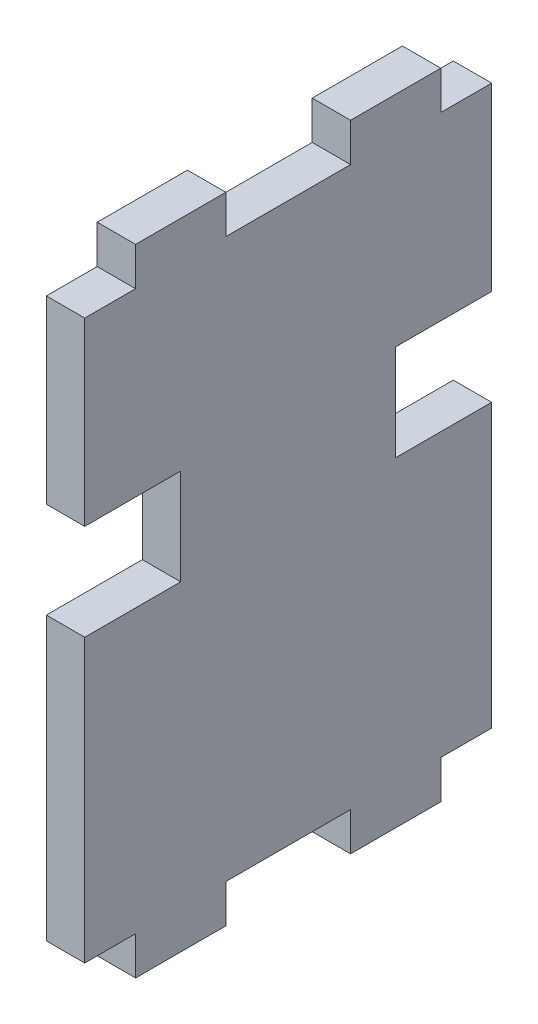
SolidWorks part; units mm, degrees
ref_plane "Front Plane" through (0, 0, 0) normal (0, 0, 1) x (1, 0, 0)
ref_plane "Top Plane" through (0, 0, 0) normal (0, 1, 0) x (1, 0, 0)
ref_plane "Right Plane" through (0, 0, 0) normal (1, 0, 0) x (0, 0, -1)
sketch "Sketch1" plane through (0, 0, 0) normal (0, 1, 0) x (1, 0, 0)
  line L1 (0, 0) -> (20, 0)
  line L2 (0, 0) -> (0, 50)
  line L3 (0, 50) -> (20, 50)
  line L4 (20, 0) -> (20, 50)
  dimension "D1" = 50
  dimension "D2" = 20
extrude "Boss-Extrude2" add sketch "Sketch1" along normal blind 4
sketch "Sketch3" plane through (0, 4, 0) normal (0, 1, 0) x (1, 0, 0)
  line L0 (7.85, 10.95) -> (6.4, 25)
  line L1 (6.4, 25) -> (7.85, 39.05)
  line L2 (12.15, 39.05) -> (13.6, 25)
  line L3 (13.6, 25) -> (12.15, 10.95)
  line L4 (6.4, 25) -> (13.6, 25) construction
  line L5 (20, 50) -> (0, 50) construction
  line L6 (0, 50) -> (0, 0) construction
  arc A0 (12.15, 39.05) -> (7.85, 39.05) centre (10, 39.05) ccw
  arc A1 (7.85, 10.95) -> (12.15, 10.95) centre (10, 10.95) ccw
  point P12 (10, 50)
  point P15 (0, 25)
  dimension "D1" = 4.3
  dimension "D2" = 4.3
  dimension "D3" = 28.1
  dimension "D4" = 14.05
  dimension "D5" = 7.2
  dimension "D6" = 3.6
  dimension "D7" = 3.6
extrude "Cut-Extrude1" cut sketch "Sketch3" against normal blind 2
sketch "Sketch7" plane through (0, 4, 0) normal (0, 1, 0) x (1, 0, 0)
  line L0 (17.1141, 39.7659) -> (18.6, 25)
  line L1 (18.6, 25) -> (17.1141, 10.2341)
  line L4 (10, 46.2) -> (0, 46.2)
  line L5 (0, 50) -> (0, 0) construction
  line L6 (10, 3.8) -> (0, 3.8)
  line L7 (0, 3.8) -> (0, 0)
  line L8 (20, 50) -> (0, 50)
  line L9 (20, 50) -> (20, 0)
  line L10 (20, 0) -> (0, 0)
  line L11 (0, 50) -> (0, 46.2)
  arc A0 (17.1141, 39.7659) -> (10, 46.2) centre (10, 39.05) ccw
  arc A1 (10, 3.8) -> (17.1141, 10.2341) centre (10, 10.95) ccw
  arc A3 (12.15, 39.05) -> (7.85, 39.05) centre (10, 39.05) ccw construction
  arc A4 (7.85, 10.95) -> (12.15, 10.95) centre (10, 10.95) ccw construction
  dimension "D1" = 5
  dimension "D2" = 5
  dimension "D3" = 5
extrude "Cut-Extrude2" cut sketch "Sketch7" against normal through all both and the other way through all
sketch "Sketch8" plane through (0, 0, 0) normal (0, -1, 0) x (1, 0, 0)
  line L1 (0, -46.2) -> (-64.2367, -46.2)
  line L2 (0, -46.2) -> (0, -3.8)
  line L3 (0, -3.8) -> (-64.2367, -3.8)
  line L4 (-64.2367, -46.2) -> (-64.2367, -3.8)
extrude "Boss-Extrude4" add sketch "Sketch8" against normal blind 4
sketch "Sketch9" plane through (0, 2, 0) normal (0, 1, 0) x (1, 0, 0)
  circle A0 centre (10, 25) radius 1.7
  dimension "D1" = 3.4
  dimension "D2" = 3.6
extrude "Cut-Extrude4" cut sketch "Sketch9" against normal blind 4
sketch "Sketch10" plane through (0, 0, 0) normal (0, -1, 0) x (1, 0, 0)
  line L0 (-64.2367, -46.2) -> (10, -46.2) construction
  line L1 (-64.2367, -3.8) -> (-11, -3.8)
  line L2 (-64.2367, -3.8) -> (-64.2367, -46.2)
  line L3 (-64.2367, -46.2) -> (-11, -46.2)
  line L4 (-11, -3.8) -> (-11, -46.2)
  circle A0 centre (10, -25) radius 1.7
  dimension "D1" = 21
extrude "Cut-Extrude5" cut sketch "Sketch10" against normal blind 4
sketch "Sketch11" plane through (0, 0, 0) normal (0, -1, 0) x (1, 0, 0)
  line L0 (-11, -46.2) -> (10, -46.2) construction
  line L1 (-11, -3.8) -> (-5, -3.8)
  line L2 (-11, -3.8) -> (-11, -46.2)
  line L3 (-11, -46.2) -> (-5, -46.2)
  line L4 (-5, -3.8) -> (-5, -46.2)
  dimension "D1" = 6
extrude "Boss-Extrude5" add sketch "Sketch11" along normal blind 62.2
sketch "Sketch13" plane through (-5, 0, 0) normal (1, 0, 0) x (0, 0, -1)
  line L0 (46.2, -62.2) -> (46.2, 0) construction
  line L1 (3.8, -62.2) -> (46.2, -62.2)
  line L2 (3.8, -62.2) -> (3.8, -58.2)
  line L3 (3.8, -58.2) -> (46.2, -58.2)
  line L4 (46.2, -62.2) -> (46.2, -58.2)
  dimension "D1" = 4
extrude "Boss-Extrude6" add sketch "Sketch13" along normal blind 30
sketch "Sketch14" plane through (0, -58.2, 0) normal (0, 1, 0) x (1, 0, 0)
  line L0 (-5, 46.2) -> (-5, 3.8) construction
  line L2 (-5, 3.8) -> (15.3097, 16.5261)
  line L3 (-5, 46.2) -> (15.3097, 33.4739)
  circle A0 centre (10, 25) radius 5
  arc A1 (15.3097, 16.5261) -> (15.3097, 33.4739) centre (10, 25) ccw
  line M6 (-5, 3.8) -> (25, 3.8)
  line M7 (25, 3.8) -> (25, 46.2)
  line M8 (25, 46.2) -> (-5, 46.2)
  dimension "D1" = 10
  dimension "D4" = 20
  dimension "D2" = 15
  dimension "D3" = 21.2
extrude "Cut-Extrude6" cut sketch "Sketch14" against normal blind 30 contours A1 L2 L3 M6 M7 M8 | A0 region at (5.4307, -58.2, -9.7229) region at (10, -58.2, -25)
sketch "Sketch15" plane through (0, 0, -3.8) normal (0, 0, 1) x (1, 0, 0)
  line L0 (-5, -62.2) -> (-11, -62.2) construction
  line L1 (-11, 4) -> (-9, 4)
  line L2 (-11, 4) -> (-11, -62.2)
  line L3 (-11, -62.2) -> (-9, -62.2)
  line L4 (-9, 4) -> (-9, -62.2)
  dimension "D1" = 4
extrude "Cut-Extrude7" cut sketch "Sketch15" against normal through all both and the other way through all
sketch "Sketch18" plane through (0, 0, -3.8) normal (0, 0, 1) x (1, 0, 0)
  line L1 (-9, 4) -> (23.8478, 4)
  line L2 (-9, 4) -> (-9, 0)
  line L3 (-9, 0) -> (23.8478, 0)
  line L4 (23.8478, 4) -> (23.8478, 0)
  line L5 (-9, -62.2) -> (38.635, -62.2)
  line L6 (-9, -62.2) -> (-9, -58.2)
  line L7 (-9, -58.2) -> (38.635, -58.2)
  line L8 (38.635, -62.2) -> (38.635, -58.2)
extrude "Cut-Extrude10" cut sketch "Sketch18" against normal through all both and the other way through all
sketch "Sketch19" plane through (0, 0, 0) normal (0, 1, 0) x (1, 0, 0)
  line L0 (-5, 46.2) -> (-5, 3.8) construction
  line L1 (-5, 40.9) -> (-9, 40.9)
  line L2 (-5, 40.9) -> (-5, 31.5)
  line L3 (-5, 31.5) -> (-9, 31.5)
  line L4 (-9, 40.9) -> (-9, 31.5)
  line L5 (-9, 46.2) -> (-9, 3.8) construction
  line L7 (-5, 18.5) -> (-9, 18.5)
  line L8 (-5, 18.5) -> (-5, 9.1)
  line L9 (-5, 9.1) -> (-9, 9.1)
  line L10 (-9, 18.5) -> (-9, 9.1)
  dimension "D1" = 5.3
  dimension "D2" = 9.4
  dimension "D3" = 5.3
  dimension "D4" = 9.4
sketch "Sketch20" plane through (0, -58.2, 0) normal (0, -1, 0) x (1, 0, 0)
  line L0 (-5, -46.2) -> (-5, -3.8) construction
  line L1 (-5, -9.1) -> (-9, -9.1)
  line L2 (-5, -9.1) -> (-5, -18.5)
  line L3 (-5, -18.5) -> (-9, -18.5)
  line L4 (-9, -9.1) -> (-9, -18.5)
  line L5 (-9, -46.2) -> (-9, -3.8) construction
  line L7 (-5, -31.5) -> (-9, -31.5)
  line L8 (-5, -31.5) -> (-5, -40.9)
  line L9 (-5, -40.9) -> (-9, -40.9)
  line L10 (-9, -31.5) -> (-9, -40.9)
  dimension "D1" = 5.3
  dimension "D2" = 9.4
  dimension "D3" = 9.4
  dimension "D4" = 5.3
sketch "Sketch21" plane through (-5, 0, 0) normal (1, 0, 0) x (0, 0, -1)
  line L2 (46.2, -18.8) -> (46.2, -28.8)
  line L4 (3.8, -18.8) -> (3.8, -28.8)
  line L6 (46.2, -18.8) -> (36.2, -18.8)
  line L8 (46.2, -28.8) -> (36.2, -28.8)
  line L9 (36.2, -18.8) -> (36.2, -28.8)
  line L10 (3.8, -18.8) -> (13.8, -18.8)
  line L12 (3.8, -28.8) -> (13.8, -28.8)
  line L13 (13.8, -18.8) -> (13.8, -28.8)
  dimension "D2" = 10
  dimension "D4" = 10
  dimension "D5" = 10
extrude "Cut-Extrude11" cut sketch "Sketch21" against normal blind 4
extrude "Boss-Extrude9" add sketch "Sketch19" along normal blind 4
extrude "Boss-Extrude10" add sketch "Sketch20" along normal blind 4
